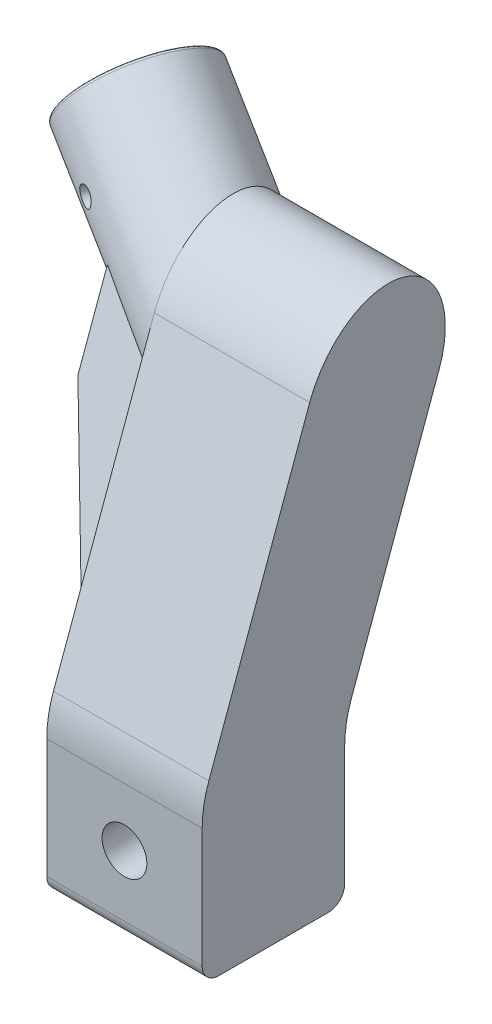
SolidWorks part; units mm, degrees
ref_plane "Front Plane" through (0, 0, 0) normal (0, 0, 1) x (1, 0, 0)
ref_plane "Top Plane" through (0, 0, 0) normal (0, 1, 0) x (1, 0, 0)
ref_plane "Right Plane" through (0, 0, 0) normal (1, 0, 0) x (0, 0, -1)
sketch "Sketch14" plane through (0, 0, 0) normal (0, 0, 1) x (1, 0, 0)
  line L0 (0, 0) -> (0, -50000) construction
ref_plane "Plane4" through (0, 0, 0) normal (0.342, 0, -0.9397) x (0, -1, 0)
sketch "Sketch1" plane through (0, 0, 0) normal (0.342, 0, -0.9397) x (-0.9397, 0, -0.342)
  line L4 (0, 0) -> (24.9266, 16.6932)
  dimension "D1" = 33.81
  dimension "D2" = 30
ref_plane "Plane1" through (-23.4234, 16.6932, -8.5254) normal (-0.7808, 0.5564, -0.2842) x (-0.0215, -0.4785, -0.8778)
sketch "Sketch2" plane through (-23.4234, 16.6932, -8.5254) normal (-0.7808, 0.5564, -0.2842) x (-0.0215, -0.4785, -0.8778)
  circle A0 centre (0, 0) radius 10.05
  circle A1 centre (0, 0) radius 12.05
  dimension "D1" = 20.1
  dimension "D2" = 2
extrude "Boss-Extrude1" add sketch "Sketch2" against normal up to surface (37.4704 mm away) up to plane "Right Plane"
sketch "Sketch6" plane through (0, 0, 0) normal (0, 0, 1) x (1, 0, 0)
  line L0 (-30.4168, 6.8803) -> (-16.4299, 26.5062) construction
  line L1 (0, 14.797) -> (-16.4299, 26.5062) construction
  line L2 (-30.4168, 6.8803) -> (0, -14.797) construction
  line L3 (-23.4234, 16.6932) -> (-23.4234, -64.2099) construction
  dimension "D1" = 80.9031
sketch "Sketch15" plane through (0, 0, 0) normal (0.342, 0, -0.9397) x (0, -1, 0)
  line L0 (0, 0) -> (-16.6932, 24.9266) construction
  line L1 (-6.681, 31.6317) -> (-26.7054, 18.2215) construction
  line L2 (-16.6932, 24.9266) -> (-2.9372, 4.3858) construction
  circle A1 centre (-9.8152, 14.6562) radius 1.7
  ellipse E0 centre (0, 0) end of major axis (-14.7945, 0.9503) minor radius 4.2905 construction
  dimension "D1" = 3.4
extrude "Cut-Extrude4" cut sketch "Sketch15" against normal through all both and the other way through all
sketch "Sketch4" plane through (0, 0, 0) normal (1, 0, 0) x (0, 0, -1)
  line L28 (-11.6979, 3.2617) -> (-31.1418, -50.1599)
  line L30 (-31.1418, -50.1599) -> (-5.3716, -50.1599) construction
  line L31 (-5.3716, -50.1599) -> (11.6979, -3.2617)
  line L34 (-31.1418, -50.1599) -> (-5.3716, -50.1599) construction
  line L35 (-31.1418, -50.1599) -> (-31.1418, -78.2599)
  line L36 (-31.1418, -78.2599) -> (-5.3716, -78.2599)
  line L37 (-5.3716, -50.1599) -> (-5.3716, -78.2599)
  line L38 (-31.1418, -50.1599) -> (-5.3716, -78.2599) construction
  line L39 (-31.1418, -78.2599) -> (-5.3716, -50.1599) construction
  ellipse E0 centre (0, 0) end of major axis (7.0195, 13.7446) minor radius 12.05 construction
  ellipse E1 centre (0, 0) end of major axis (7.0195, 13.7446) minor radius 12.05 (11.6979, -3.2617) -> (-11.6979, 3.2617) ccw
  point P16 (-18.2567, -64.2099)
  ellipse M1 centre (0, 0) end of major axis (7.0195, 13.7446) minor radius 12.05
  ellipse M2 centre (0, 0) end of major axis (5.8544, 11.4633) minor radius 10.05
  dimension "D1" = 20
  dimension "D2" = 14.05
  dimension "D3" = 28.1
extrude "Boss-Extrude2" add sketch "Sketch4" along normal blind 28.098 contours M1 M2 | M2 | M1 | M1 | M2 region at (0, -44.6938, 14.3294) region at (0, 12.2714, 4.2091) region at (0, 0, 0)
sketch "Sketch10" plane through (0, 0, 5.3716) normal (0, 0, -1) x (-1, 0, 0)
  line L1 (-28.098, -78.2599) -> (0, -78.2599) construction
  line L6 (0, -78.2599) -> (0, -50.1599)
  line L7 (0, -50.1599) -> (-28.098, -50.1599)
  line L12 (-28.098, -50.1599) -> (-28.098, -78.2599)
  line L13 (-28.098, -78.2599) -> (0, -78.2599)
  line L14 (0, -78.2599) -> (0, -50.1599) construction
  line L15 (0, -50.1599) -> (-28.098, -50.1599) construction
  line L16 (-28.098, -50.1599) -> (-28.098, -78.2599) construction
  line L17 (-28.098, -78.2599) -> (0, -78.2599) construction
  circle A0 centre (-14.049, -64.2099) radius 11.074
  point P16 (-14.049, -78.2599)
  dimension "D2" = 22.148
  dimension "D3" = 0
  dimension "D1" = 14.05
extrude "Cut-Extrude2" cut sketch "Sketch10" against normal blind 7.874 and the other way through all
sketch "Sketch11" plane through (0, 0, 13.2456) normal (0, 0, -1) x (-1, 0, 0)
  circle A0 centre (-14.049, -64.2099) radius 4.05
  circle A1 centre (-14.049, -64.2099) radius 11.074
  circle A2 centre (-14.049, -64.2099) radius 11.074 construction
  dimension "D2" = 8.1
  dimension "D1" = 0
extrude "Cut-Extrude3" cut sketch "Sketch11" against normal through all both and the other way through all
ref_plane "Plane3" through (0, 0, 0) normal (0, -0.342, -0.9397) x (1, 0, 0)
sketch "Sketch12" plane through (0, 0, 0) normal (0, -0.342, -0.9397) x (1, 0, 0)
  line L0 (0, 48.9721) -> (0, -0.9359) construction
  line L2 (0, 47.7836) -> (0, 15.3878)
  line L4 (-11.7911, 15.3878) -> (0, 47.7836)
  line L5 (-11.7911, 15.3878) -> (0, 15.3878)
  dimension "D1" = 11.08
  dimension "D2" = 20
fillet "Fillet8" radius 20 2 edges at (14.049, -50.1599, 5.3716) (14.049, -50.1599, 31.1418)
fillet "Fillet9" radius 3 2 edges at (14.049, -78.2599, 5.3716) (14.049, -78.2599, 31.1418)
fillet "Fillet10" radius 0.5 2 edges at (-30.4168, 6.8803, -8.5254) (-29.2561, 8.509, -8.5254)
extrude "Boss-Extrude6" add sketch "Sketch12" along normal mid plane 18
sketch "Sketch13" plane through (0, -14.4598, 5.2629) normal (0, 0.9397, -0.342) x (1, 0, 0)
  line L5 (-11.7911, -9) -> (0, -9)
  line L6 (0, -9) -> (0, -0.7364)
  line L7 (0, -0.7364) -> (0, 9)
  line L8 (0, 9) -> (-11.7911, 9)
  line L9 (-11.7911, 9) -> (-11.7911, -9)
  line L10 (-11.7911, -9) -> (0, -9)
  line L11 (0, -9) -> (0, -0.7364)
  line L12 (0, -0.7364) -> (0, 9)
  line L13 (0, 9) -> (-11.7911, 9)
  line L14 (-11.7911, 9) -> (-11.7911, -9)
  dimension "D1" = 0
extrude "Boss-Extrude7" add sketch "Sketch13" along normal up to surface (5.8089 mm away) up to face at (-30.0264, 6.602, -8.3833)
ref_plane "Plane2" [suppressed] through (0, 0, 15) normal (0, 0, 1) x (1, 0, 0)
mirror "Mirror1" [suppressed] about plane through (0, 0, 15) normal (0, 0, 1) of bodies 107
delete or keep bodies "Body-Delete/Keep 1" [suppressed] type delete bodies bodies 107
